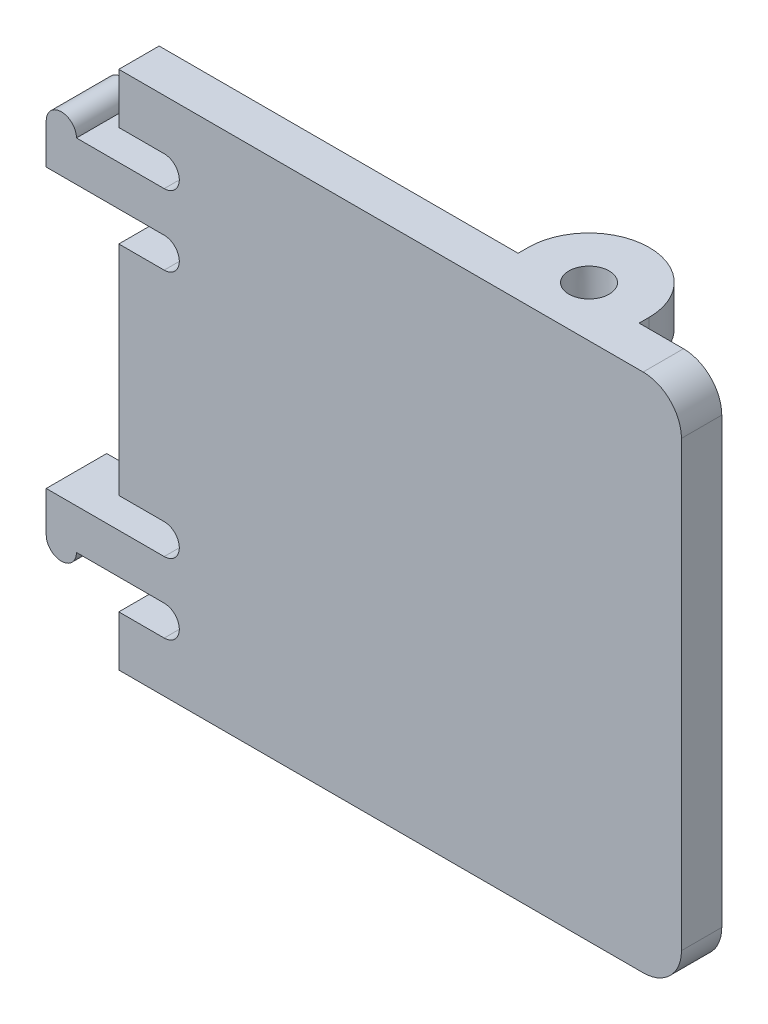
SolidWorks part; units mm, degrees
ref_plane "前视基准面" through (0, 0, 0) normal (0, 0, 1) x (1, 0, 0)
ref_plane "上视基准面" through (0, 0, 0) normal (0, 1, 0) x (1, 0, 0)
ref_plane "右视基准面" through (0, 0, 0) normal (1, 0, 0) x (0, 0, -1)
other "Configuration Table"
sketch "草图1" plane through (0, 0, 0) normal (0, 0, 1) x (1, 0, 0)
  line L3 (-11.9424, 3.3113) -> (-11.9424, -22.4887)
  line L4 (-11.9424, 6.4113) -> (-11.9424, -25.5887) construction
  line L6 (-11.9424, -22.4887) -> (14.0576, -22.4887)
  line L7 (15.9576, -20.5887) -> (15.9576, 1.4113)
  line L8 (14.0576, 3.3113) -> (-11.9424, 3.3113)
  line L9 (-11.9424, -22.4887) -> (14.0576, -22.4887)
  line L10 (15.9576, -20.5887) -> (15.9576, 1.4113)
  line L11 (14.0576, 3.3113) -> (-11.9424, 3.3113)
  arc A4 (14.0576, -22.4887) -> (15.9576, -20.5887) centre (14.0576, -20.5887) ccw
  arc A5 (15.9576, 1.4113) -> (14.0576, 3.3113) centre (14.0576, 1.4113) ccw
  arc A6 (14.0576, -22.4887) -> (15.9576, -20.5887) centre (14.0576, -20.5887) ccw
  arc A7 (15.9576, 1.4113) -> (14.0576, 3.3113) centre (14.0576, 1.4113) ccw
  dimension "D1" = 0.1
extrude "凸台-拉伸1" add sketch "草图1" against normal blind 2
sketch "草图2" plane through (0, 0, -2) normal (0, 0, -1) x (-1, 0, 0)
  line L0 (11.9424, -22.4887) -> (-14.0576, -22.4887) construction
  line L1 (-5.8576, -22.4887) -> (-11.8576, -22.4887)
  line L2 (-5.8576, -22.4887) -> (-5.8576, -20.4887)
  line L3 (-5.8576, -20.4887) -> (-11.8576, -20.4887)
  line L4 (-11.8576, -22.4887) -> (-11.8576, -20.4887)
  line L5 (-14.0576, 3.3113) -> (11.9424, 3.3113) construction
  line L6 (-5.8576, 3.3113) -> (-11.8576, 3.3113)
  line L7 (-5.8576, 3.3113) -> (-5.8576, 1.3113)
  line L8 (-5.8576, 1.3113) -> (-11.8576, 1.3113)
  line L9 (-11.8576, 3.3113) -> (-11.8576, 1.3113)
  line L10 (-18.0576, -20.5887) -> (-18.0576, 1.4113) construction
  dimension "D1" = 6
  dimension "D2" = 6.2
  dimension "D3" = 2
extrude "凸台-拉伸2" add sketch "草图2" along normal blind 3.5
fillet "圆角1" radius 3 4 edges at (11.8576, 2.3113, -5.5) (5.8576, 2.3113, -5.5) (11.8576, -21.4887, -5.5) (5.8576, -21.4887, -5.5)
sketch "草图3" plane through (0, -22.4887, 0) normal (0, -1, 0) x (1, 0, 0)
  circle A0 centre (8.8741, -2.5) radius 1
  dimension "D1" = 2
extrude "切除-拉伸1" cut sketch "草图3" against normal blind 5 draft 2
sketch "草图4" plane through (0, 3.3113, 0) normal (0, 1, 0) x (1, 0, 0)
  circle A0 centre (8.8741, 2.5) radius 1
  dimension "D1" = 2
extrude "切除-拉伸2" cut sketch "草图4" against normal blind 5 draft 2
sketch "草图6" plane through (0, 0, 0) normal (0, 0, 1) x (1, 0, 0)
  line L0 (-11.9424, 3.3113) -> (-11.9424, -22.4887) construction
  line L1 (-11.9424, -0.6887) -> (-15.5424, -0.6887)
  line L2 (-11.9424, -0.6887) -> (-11.9424, -2.6887)
  line L3 (-11.9424, -2.6887) -> (-15.5424, -2.6887)
  line L4 (-15.5424, -0.6887) -> (-15.5424, -2.6887)
  line L5 (14.0576, 3.3113) -> (-11.9424, 3.3113) construction
  line L6 (-11.9424, -18.4887) -> (-15.5424, -18.4887)
  line L7 (-11.9424, -18.4887) -> (-11.9424, -16.4887)
  line L8 (-11.9424, -16.4887) -> (-15.5424, -16.4887)
  line L9 (-15.5424, -18.4887) -> (-15.5424, -16.4887)
  line L10 (-11.9424, -22.4887) -> (14.0576, -22.4887) construction
  dimension "D1" = 2
  dimension "D2" = 4
  dimension "D3" = 4
  dimension "D4" = 3.6
extrude "凸台-拉伸3" add sketch "草图6" against normal blind 3
chamfer "倒角1" distance 3 angle 45 2 edges at (-11.9424, -17.4887, -2) (-11.9424, -1.6887, -2)
sketch "草图7" plane through (0, 0, 0) normal (0, 0, 1) x (1, 0, 0)
  line L0 (-15.5424, -0.6887) -> (-15.5424, -2.6887) construction
  line L1 (-15.5424, -2.6887) -> (-11.9424, -2.6887) construction
  line L2 (-15.5424, -16.4887) -> (-15.5424, -18.4887) construction
  line L3 (-11.9424, -16.4887) -> (-15.5424, -16.4887) construction
  circle A0 centre (-14.7924, -0.6887) radius 0.75
  circle A1 centre (-14.7924, -18.4887) radius 0.75
  dimension "D1" = 1.5
  dimension "D3" = 2
  dimension "D2" = 2
extrude "凸台-拉伸4" add sketch "草图7" against normal blind 3
sketch "草图8" plane through (0, 0, 0) normal (0, 0, 1) x (1, 0, 0)
  line L1 (-8.9424, -4.1887) -> (-11.9424, -4.1887)
  line L2 (-8.9424, -4.1887) -> (-8.9424, -2.6887)
  line L3 (-8.9424, -2.6887) -> (-11.9424, -2.6887)
  line L4 (-11.9424, -4.1887) -> (-11.9424, -2.6887)
  line L5 (-11.9424, -0.6887) -> (-8.9424, -0.6887)
  line L6 (-11.9424, -0.6887) -> (-11.9424, 0.8113)
  line L7 (-11.9424, 0.8113) -> (-8.9424, 0.8113)
  line L8 (-8.9424, -0.6887) -> (-8.9424, 0.8113)
  line L9 (-11.9424, -16.4887) -> (-8.9424, -16.4887)
  line L10 (-11.9424, -16.4887) -> (-11.9424, -14.9887)
  line L11 (-11.9424, -14.9887) -> (-8.9424, -14.9887)
  line L12 (-8.9424, -16.4887) -> (-8.9424, -14.9887)
  line L13 (-11.9424, -18.4887) -> (-8.9424, -18.4887)
  line L14 (-11.9424, -18.4887) -> (-11.9424, -19.9887)
  line L15 (-11.9424, -19.9887) -> (-8.9424, -19.9887)
  line L16 (-8.9424, -18.4887) -> (-8.9424, -19.9887)
  dimension "D1" = 3
  dimension "D2" = 1.5
extrude "切除-拉伸3" cut sketch "草图8" against normal up to next
fillet "圆角2" radius 0.75 8 edges at (-8.9424, -2.6887, -1) (-8.9424, 0.8113, -1) (-8.9424, -18.4887, -1) (-8.9424, -14.9887, -1) (-8.9424, -19.9887, -1) (-8.9424, -16.4887, -1) (-8.9424, -4.1887, -1) (-8.9424, -0.6887, -1)
